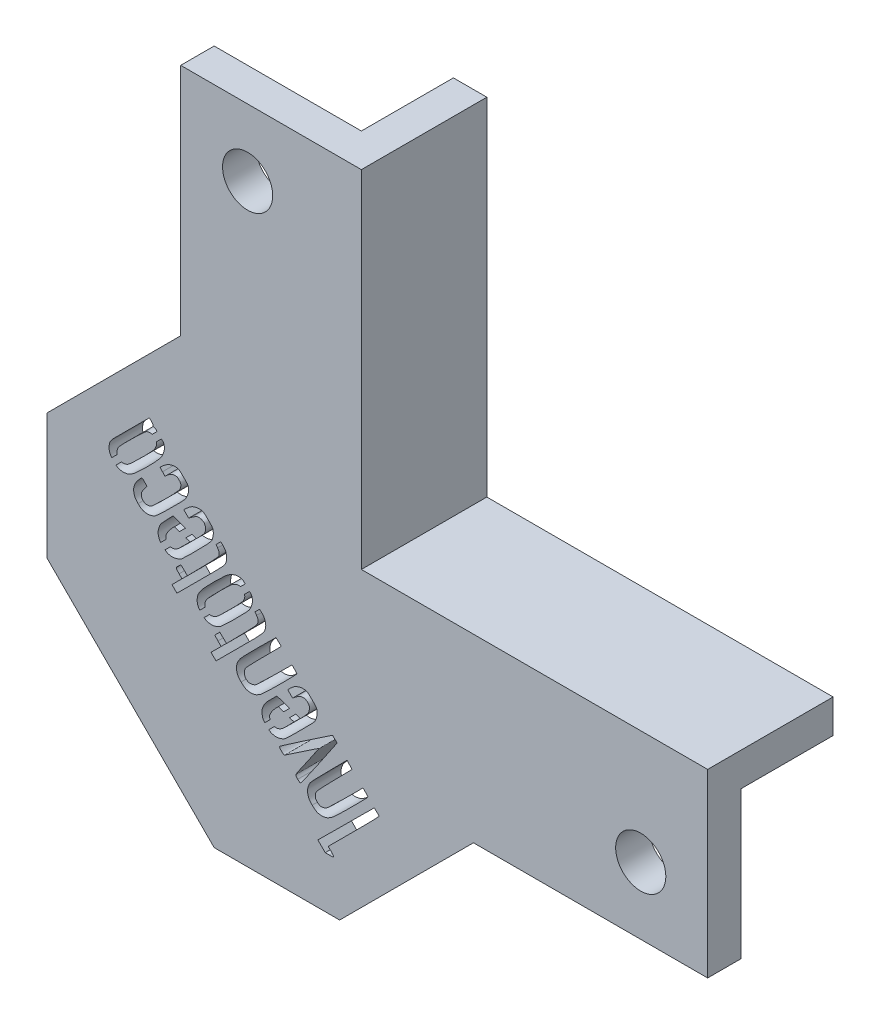
SolidWorks part; units mm, degrees
ref_plane "Alzado" through (0, 0, 0) normal (0, 0, 1) x (1, 0, 0)
ref_plane "Planta" through (0, 0, 0) normal (0, 1, 0) x (1, 0, 0)
ref_plane "Vista lateral" through (0, 0, 0) normal (1, 0, 0) x (0, 0, -1)
sketch "Croquis1" plane through (0, 0, 0) normal (0, 0, 1) x (1, 0, 0)
  line L0 (21.6725, 1.0791) -> (12.8725, 1.0791)
  line L5 (20.8725, 1.0791) -> (3.3725, 1.0791) construction
  line L6 (12.8725, 1.0791) -> (12.8725, -30.4209)
  line L7 (12.8725, -30.4209) -> (44.3725, -30.4209)
  line L8 (44.3725, -39.9209) -> (44.3725, -22.4209) construction
  line L9 (44.3725, -30.4209) -> (44.3725, -21.6209)
  line L10 (44.3725, -21.6209) -> (21.6725, -21.6209)
  line L12 (21.6725, -21.6209) -> (21.6725, 1.0791)
  line L13 (20.8725, -22.4209) -> (20.8725, 1.0791) construction
  line L14 (44.3725, -22.4209) -> (20.8725, -22.4209) construction
  circle A1 centre (16.8725, -2.9209) radius 1.5
  circle A2 centre (40.3725, -26.4209) radius 1.5
  dimension "D1" = 3
  dimension "D2" = 0.8
  dimension "D3" = 0.8
  dimension "D4" = 4
  dimension "D5" = 4
extrude "Saliente-Extruir1" add sketch "Croquis1" along normal blind 2
sketch "Croquis2" plane through (0, 0, 2) normal (0, 0, 1) x (1, 0, 0)
  line L0 (21.6725, 1.0791) -> (23.6725, 1.0791)
  line L1 (23.6725, 1.0791) -> (23.6725, -19.6209)
  line L2 (23.6725, -19.6209) -> (44.3725, -19.6209)
  line L3 (44.3725, -19.6209) -> (44.3725, -21.6209)
  line L4 (44.3725, -21.6209) -> (21.6725, -21.6209)
  line L5 (21.6725, -21.6209) -> (21.6725, 1.0791)
  dimension "D1" = 2
extrude "Saliente-Extruir2" add sketch "Croquis2" against normal blind 7.5
chamfer "Chaflán1" distance 4 angle 45 1 edges at (12.8725, -30.4209, 1)
sketch "Croquis3" plane through (0, 0, 2) normal (0, 0, 1) x (1, 0, 0)
  line L0 (32.3725, -19.6209) -> (23.6725, -19.6209)
  line L1 (23.6725, -10.9209) -> (4.8725, -10.9209)
  line L2 (32.3725, -19.6209) -> (32.3725, -38.4209)
  line L3 (32.3725, -38.4209) -> (4.8725, -38.4209)
  line L4 (4.8725, -10.9209) -> (4.8725, -38.4209)
  line L5 (23.6725, -19.6209) -> (23.6725, -10.9209)
  line L6 (23.6725, -19.6209) -> (23.6725, 1.0791) construction
  line L7 (44.3725, -19.6209) -> (23.6725, -19.6209) construction
  line L8 (12.8725, 1.0791) -> (12.8725, -26.4209) construction
  circle A0 centre (16.8725, -2.9209) radius 1.5 construction
  point P0 (35.2752, -19.6209)
  dimension "D1" = 8
  dimension "D2" = 8
extrude "Saliente-Extruir3" add sketch "Croquis3" against normal up to surface (2 mm away) up to face at (24.9582, -18.3352, 0)
chamfer "Chaflán2" distance 10 angle 45 5 edges at (4.8725, -38.4209, 1) (32.3725, -38.4209, 1) (4.8725, -10.9209, 1) (12.8725, -10.9209, 1) (32.3725, -30.4209, 1)
sketch "Croquis5" plane through (0, 0, 2) normal (0, 0, 1) x (1, 0, 0)
  line L101 (22.1338, -29.4646) -> (22.2205, -29.3331)
  line L102 (21.9537, -29.0664) -> (21.8212, -29.1522)
  line L103 (22.2205, -29.3331) -> (21.9537, -29.0664)
  line L104 (22.9663, -30.0879) -> (22.8171, -29.9252)
  line L105 (23.115, -30.2502) -> (22.9663, -30.0879)
  line L106 (22.0537, -31.3338) -> (23.115, -30.2502)
  line L107 (23.7698, -30.8824) -> (22.7028, -31.9495)
  line L108 (23.9208, -31.0332) -> (23.7698, -30.8824)
  line L109 (22.8171, -29.9252) -> (21.711, -31.0448)
  line L110 (20.2604, -28.9176) -> (20.0263, -29.1676)
  line L111 (19.5613, -28.3382) -> (19.731, -28.1996)
  line L112 (19.2698, -28.0468) -> (19.5613, -28.3382)
  line L113 (19.4261, -27.8905) -> (19.2698, -28.0468)
  line L114 (20.8043, -27.923) -> (20.7155, -27.8291)
  line L115 (20.8947, -28.0106) -> (20.8043, -27.923)
  line L116 (21.011, -28.2008) -> (21.0102, -28.2016)
  line L117 (21.0136, -28.2114) -> (21.011, -28.2008)
  line L118 (18.1359, -30.6851) -> (18.4694, -30.3516)
  line L119 (19.3823, -29.4387) -> (19.7472, -29.0738)
  line L120 (20.0263, -29.1676) -> (19.7472, -29.0738)
  line L121 (18.7262, -25.848) -> (18.5661, -25.7014)
  line L122 (18.8867, -25.995) -> (18.7262, -25.848)
  line L123 (17.8139, -27.081) -> (18.8867, -25.995)
  line L124 (19.525, -26.6376) -> (18.4515, -27.6982)
  line L125 (19.6694, -26.7821) -> (19.525, -26.6376)
  line L126 (18.5661, -25.7014) -> (17.5655, -26.6898)
  line L127 (15.1002, -27.6067) -> (15.2844, -27.8035)
  line L128 (15.2055, -27.1034) -> (14.9078, -27.4012)
  line L129 (15.4128, -27.2975) -> (15.2055, -27.1034)
  line L130 (17.5868, -24.7221) -> (17.313, -24.996)
  line L131 (17.7195, -24.8425) -> (17.5868, -24.7221)
  line L132 (14.9831, -28.7009) -> (16.3714, -27.3125)
  line L133 (14.6851, -28.4028) -> (14.9831, -28.7009)
  line L134 (15.2844, -27.8035) -> (14.6851, -28.4028)
  line L135 (14.9078, -27.4012) -> (15.1002, -27.6067)
  line L136 (15.6113, -27.4834) -> (15.4128, -27.2975)
  line L137 (16.5166, -26.5629) -> (15.6113, -27.4834)
  line L138 (17.313, -24.996) -> (17.4085, -25.1299)
  line L139 (16.728, -23.8437) -> (16.7279, -23.8435)
  line L140 (16.4374, -24.1343) -> (16.728, -23.8437)
  line L141 (14.0131, -26.5586) -> (14.3374, -26.2343)
  line L142 (12.3482, -26.066) -> (12.6462, -26.364)
  line L143 (12.9491, -25.4651) -> (12.3482, -26.066)
  line L144 (14.1896, -24.2154) -> (13.272, -25.1474)
  line L145 (14.9807, -22.6768) -> (15.0771, -22.8027)
  line L146 (15.2725, -22.385) -> (14.9807, -22.6768)
  line L147 (15.3914, -22.5086) -> (15.2725, -22.385)
  line L148 (12.6462, -26.364) -> (14.0486, -24.9616)
  line L149 (12.7784, -25.2941) -> (12.9491, -25.4651)
  line L150 (13.272, -25.1474) -> (13.0859, -24.9613)
  line L151 (12.4918, -23.002) -> (12.7939, -23.1024)
  line L152 (12.3893, -23.1052) -> (12.4918, -23.002)
  line L153 (11.6745, -24.2218) -> (12.0003, -23.896)
  line L154 (12.4077, -22.4815) -> (12.0343, -22.8714)
  line L155 (13.1109, -22.7223) -> (12.4077, -22.4815)
  line L156 (13.1579, -22.7384) -> (13.1109, -22.7223)
  line L157 (12.7939, -23.1024) -> (13.1579, -22.7384)
  line L158 (11.9318, -20.6687) -> (12.0141, -20.5864)
  line L159 (11.7838, -20.5072) -> (11.9318, -20.6687)
  line L160 (11.636, -20.3458) -> (11.7838, -20.5072)
  line L161 (11.8156, -20.1828) -> (11.636, -20.3458)
  line L162 (13.1533, -20.2692) -> (12.8873, -20.0029)
  line L163 (10.7039, -21.9191) -> (10.8499, -21.7242)
  line L164 (10.8499, -21.7242) -> (10.7175, -21.5783)
  line L165 (9.007, -21.5496) -> (9.335, -21.2216)
  line L166 (11.4289, -19.1277) -> (11.7197, -18.8368)
  line L167 (11.7602, -18.8774) -> (11.7197, -18.8368)
  line L168 (24.5869, -31.7089) -> (24.4416, -31.577)
  line L169 (21.6908, -34.9461) -> (23.2073, -33.4296)
  line L170 (21.8644, -35.1198) -> (21.6908, -34.9461)
  line L171 (21.5113, -35.3625) -> (21.7474, -35.364)
  line L172 (21.0722, -34.9235) -> (21.5112, -35.3625)
  line L173 (22.7571, -33.2501) -> (21.0722, -34.9235)
  line L174 (24.4416, -31.577) -> (22.7571, -33.2501)
  line L175 (16.8244, -23.94) -> (16.728, -23.8437)
  line L176 (17.1301, -24.2886) -> (17.1292, -24.2896)
  line L177 (17.133, -24.2986) -> (17.1301, -24.2886)
  line L178 (14.2709, -26.8134) -> (14.598, -26.4862)
  line L179 (16.6861, -24.3981) -> (16.9832, -24.1011)
  line L180 (17.0216, -24.1387) -> (16.9832, -24.1011)
  line L181 (14.0184, -22.7485) -> (13.8067, -22.9606)
  line L182 (13.349, -22.1259) -> (13.5387, -21.984)
  line L183 (13.0548, -21.8317) -> (13.349, -22.1259)
  line L184 (13.264, -21.6424) -> (13.0548, -21.8317)
  line L185 (14.441, -21.5561) -> (14.357, -21.4709)
  line L186 (14.6862, -21.8005) -> (14.5965, -21.712)
  line L187 (11.9331, -24.4757) -> (12.2602, -24.1478)
  line L188 (13.1778, -23.2311) -> (13.5397, -22.8691)
  line L189 (13.8067, -22.9606) -> (13.5397, -22.8691)
  line L190 (8.7473, -21.2967) -> (9.071, -20.973)
  line L191 (8.8451, -20.2606) -> (8.7972, -20.3096)
  line L192 (10.9676, -18.1383) -> (8.8451, -20.2606)
  line L193 (11.4646, -18.5795) -> (11.4523, -18.5669)
  line L194 (11.1713, -18.8727) -> (11.4646, -18.5795)
  line L195 (18.7012, -29.2114) -> (19.0213, -29.3178)
  line L196 (18.6211, -28.6954) -> (18.281, -29.0356)
  line L197 (19.0213, -29.3178) -> (19.3864, -28.9526)
  line L198 (18.5654, -29.3481) -> (18.7012, -29.2114)
  line L199 (19.3864, -28.9526) -> (19.3274, -28.9328)
  line L200 (17.8967, -30.4424) -> (18.2171, -30.122)
  line L201 (19.3274, -28.9328) -> (18.6211, -28.6954)
  spline S48 degree 3 number of poles 84 (19.8674, -32.3833) -> (22.1338, -29.4646)
  spline S49 degree 3 number of poles 313 (21.8212, -29.1522) -> (19.8674, -32.3833)
  spline S50 degree 3 number of poles 66 (22.7028, -31.9495) -> (22.0537, -31.3338)
  spline S51 degree 3 number of poles 147 (20.7312, -33.2907) -> (23.9208, -31.0332)
  spline S52 degree 3 poles (21.711, -31.0448) (21.6605, -31.0959) (21.5594, -31.1982) (21.4079, -31.3518) (21.2723, -31.4894) (21.1526, -31.6112) (21.0489, -31.7171) (20.9578, -31.8109) (20.8793, -31.8925) (20.8134, -31.9619) (20.7568, -32.0227) (20.7093, -32.075) (20.6711, -32.1187) (20.6391, -32.1579) (20.613, -32.1922) (20.5927, -32.2214) (20.5755, -32.2496) (20.5613, -32.2768) (20.5494, -32.3023) (20.5373, -32.3308) (20.5249, -32.362) (20.5123, -32.3961) (20.5005, -32.4308) (20.4894, -32.466) (20.479, -32.5018) (20.4697, -32.5356) (20.4616, -32.5674) (20.455, -32.5972) (20.4503, -32.6273) (20.4481, -32.6577) (20.448, -32.6882) (20.4496, -32.7208) (20.4528, -32.7556) (20.4577, -32.7924) (20.4642, -32.8288) (20.472, -32.8647) (20.4811, -32.9002) (20.4922, -32.9379) (20.5057, -32.9777) (20.5222, -33.0191) (20.5413, -33.0586) (20.5631, -33.096) (20.5871, -33.1312) (20.6162, -33.1688) (20.6507, -33.2085) (20.6905, -33.25) (20.7176, -33.2771) (20.7312, -33.2907) knots 0 0 0 0 0.076954 0.153907 0.23086 0.283751 0.336642 0.389535 0.423665 0.457793 0.491917 0.512625 0.533334 0.554061 0.56676 0.579445 0.592109 0.602148 0.612198 0.622257 0.63523 0.648193 0.661148 0.67443 0.687719 0.701028 0.711935 0.722825 0.733689 0.744526 0.755392 0.766273 0.779524 0.79276 0.805987 0.819044 0.832109 0.845188 0.861108 0.877014 0.892899 0.908066 0.923252 0.938439 0.958952 0.979467 1 1 1 1
  spline S53 degree 3 poles (19.731, -28.1996) (19.7421, -28.1912) (19.7644, -28.1743) (19.7982, -28.1493) (19.8326, -28.1251) (19.868, -28.1022) (19.9041, -28.0804) (19.9384, -28.0611) (19.9706, -28.044) (20.0007, -28.0296) (20.0301, -28.0177) (20.0586, -28.0087) (20.086, -28.0018) (20.1136, -27.9962) (20.1414, -27.9918) (20.1693, -27.9884) (20.1955, -27.9865) (20.2197, -27.9857) (20.242, -27.9865) (20.2638, -27.9895) (20.2849, -27.9953) (20.3051, -28.0031) (20.3263, -28.013) (20.3485, -28.0245) (20.3715, -28.0378) (20.3937, -28.0521) (20.415, -28.0672) (20.4354, -28.0833) (20.4553, -28.1009) (20.4744, -28.12) (20.4926, -28.1407) (20.5088, -28.1621) (20.5232, -28.1838) (20.5356, -28.2058) (20.5462, -28.2282) (20.5549, -28.2511) (20.5615, -28.2742) (20.5661, -28.2978) (20.5685, -28.3216) (20.569, -28.3455) (20.5682, -28.371) (20.5663, -28.3981) (20.5631, -28.4266) (20.5589, -28.4547) (20.5537, -28.4822) (20.5474, -28.509) (20.5388, -28.5385) (20.5268, -28.5702) (20.511, -28.6036) (20.4911, -28.6395) (20.4664, -28.6772) (20.4371, -28.7166) (20.4012, -28.7608) (20.3588, -28.81) (20.3099, -28.8641) (20.2769, -28.8998) (20.2604, -28.9176) knots 0 0 0 0 0.023887 0.04776 0.071615 0.095597 0.119599 0.143636 0.16267 0.181678 0.20065 0.216663 0.232697 0.248731 0.264704 0.280675 0.296702 0.3094 0.322053 0.334625 0.346885 0.359222 0.371603 0.386744 0.401832 0.416908 0.431672 0.446445 0.461221 0.476881 0.492541 0.508205 0.522549 0.53689 0.551238 0.564907 0.578568 0.5922 0.605757 0.619335 0.63293 0.649283 0.665616 0.681953 0.697636 0.713316 0.728986 0.749973 0.77099 0.792012 0.819891 0.847772 0.875671 0.917131 0.958567 1 1 1 1
  spline S54 degree 3 number of poles 66 (20.6224, -27.7411) -> (19.4261, -27.8905)
  spline S55 degree 3 poles (20.7155, -27.8291) (20.7086, -27.8243) (20.6937, -27.814) (20.671, -27.7931) (20.6545, -27.7698) (20.6415, -27.7511) (20.6348, -27.7381) (20.6247, -27.7381) (20.6228, -27.7406) (20.6226, -27.7408) (20.6224, -27.741) (20.6224, -27.7411) knots 0 0 0 0 0.188249 0.405775 0.68873 0.822663 0.92833 0.992253 0.994929 0.998086 1 1 1 1
  spline S56 degree 3 poles (21.0102, -28.2016) (21.0075, -28.1941) (21.0019, -28.1791) (20.9932, -28.1567) (20.9832, -28.134) (20.9715, -28.1114) (20.958, -28.0889) (20.9432, -28.0677) (20.9275, -28.0479) (20.9113, -28.0291) (20.9002, -28.0168) (20.8947, -28.0106) knots 0 0 0 0 0.106664 0.213276 0.319826 0.436244 0.552766 0.669193 0.779404 0.889656 1 1 1 1
  spline S57 degree 3 number of poles 81 (18.1359, -30.6851) -> (21.0136, -28.2114)
  spline S58 degree 3 number of poles 96 (19.3823, -29.4387) -> (18.4694, -30.3516)
  spline S59 degree 3 number of poles 84 (18.4515, -27.6982) -> (17.8139, -27.081)
  spline S60 degree 3 number of poles 102 (18.8171, -27.9823) -> (19.6694, -26.7821)
  spline S61 degree 3 number of poles 66 (16.482, -29.0405) -> (18.8171, -27.9823)
  spline S62 degree 3 poles (17.5655, -26.6898) (17.5327, -26.7222) (17.4672, -26.7871) (17.369, -26.8845) (17.275, -26.9781) (17.1852, -27.0679) (17.0995, -27.154) (17.0185, -27.2358) (16.942, -27.3134) (16.8701, -27.3867) (16.8032, -27.4554) (16.7414, -27.5194) (16.6846, -27.5787) (16.6332, -27.6328) (16.5871, -27.6819) (16.5465, -27.7258) (16.5118, -27.7643) (16.4828, -27.7973) (16.4596, -27.8248) (16.4357, -27.8548) (16.4117, -27.888) (16.3875, -27.9242) (16.3644, -27.9608) (16.3418, -27.9976) (16.32, -28.0346) (16.3004, -28.0694) (16.283, -28.1018) (16.2682, -28.1321) (16.2554, -28.162) (16.2451, -28.1918) (16.2367, -28.221) (16.2291, -28.2518) (16.2223, -28.2842) (16.2162, -28.3181) (16.2113, -28.3512) (16.2076, -28.3836) (16.2051, -28.4152) (16.2042, -28.4468) (16.205, -28.4785) (16.2074, -28.51) (16.2111, -28.5424) (16.2158, -28.5755) (16.2217, -28.6093) (16.2283, -28.6417) (16.2356, -28.6724) (16.2437, -28.7015) (16.2539, -28.7317) (16.2668, -28.7625) (16.2826, -28.7937) (16.3014, -28.826) (16.3233, -28.859) (16.3482, -28.8926) (16.3769, -28.9279) (16.4094, -28.9645) (16.4454, -29.0028) (16.4698, -29.0279) (16.482, -29.0405) knots 0 0 0 0 0.046922 0.093844 0.140766 0.181957 0.223148 0.264339 0.299181 0.334023 0.368865 0.396731 0.424597 0.452461 0.472756 0.493052 0.513356 0.525548 0.537735 0.549913 0.564652 0.579401 0.594152 0.60874 0.623324 0.637921 0.649361 0.66079 0.672201 0.682489 0.692793 0.703103 0.714791 0.726471 0.738155 0.748906 0.759652 0.770389 0.781115 0.791849 0.802586 0.81424 0.825891 0.837548 0.847809 0.858062 0.868305 0.880162 0.892037 0.903919 0.918126 0.932328 0.946527 0.964346 0.982167 1 1 1 1
  spline S63 degree 3 poles (16.3714, -27.3125) (16.4716, -27.2122) (16.6719, -27.0117) (16.9718, -26.7106) (17.2193, -26.4608) (17.4147, -26.2625) (17.5574, -26.1143) (17.6695, -25.993) (17.7519, -25.8999) (17.8038, -25.8348) (17.8412, -25.7778) (17.8659, -25.7309) (17.8819, -25.6963) (17.8967, -25.6605) (17.9106, -25.6237) (17.9234, -25.5858) (17.9343, -25.5494) (17.9435, -25.5146) (17.9505, -25.4814) (17.9551, -25.4479) (17.9569, -25.4143) (17.9563, -25.3809) (17.954, -25.3457) (17.9502, -25.3089) (17.9448, -25.2707) (17.938, -25.2334) (17.9298, -25.1972) (17.9204, -25.1621) (17.909, -25.1263) (17.8956, -25.0899) (17.8797, -25.0533) (17.8624, -25.0187) (17.8436, -24.9863) (17.8237, -24.9561) (17.8012, -24.9265) (17.7757, -24.8979) (17.748, -24.8699) (17.729, -24.8517) (17.7195, -24.8425) knots 0 0 0 0 0.135053 0.270019 0.404809 0.469989 0.535254 0.600769 0.627289 0.653702 0.679993 0.692074 0.704181 0.716295 0.728979 0.741656 0.754349 0.765151 0.77594 0.786701 0.797302 0.807927 0.818568 0.830853 0.843119 0.855381 0.866918 0.878459 0.890001 0.902685 0.915369 0.928061 0.939535 0.951001 0.962446 0.97494 0.987458 1 1 1 1
  spline S64 degree 3 poles (17.4085, -25.1299) (17.4112, -25.134) (17.4167, -25.1422) (17.425, -25.1544) (17.433, -25.1669) (17.4407, -25.1796) (17.4481, -25.1925) (17.4552, -25.2054) (17.462, -25.2182) (17.4685, -25.231) (17.4744, -25.2436) (17.48, -25.2559) (17.4851, -25.268) (17.4896, -25.2795) (17.4937, -25.2905) (17.4971, -25.301) (17.4999, -25.3108) (17.502, -25.3198) (17.5035, -25.3279) (17.505, -25.3394) (17.5053, -25.3543) (17.5037, -25.3725) (17.5008, -25.3922) (17.4972, -25.4136) (17.4927, -25.4365) (17.4877, -25.4594) (17.4821, -25.4822) (17.4754, -25.5048) (17.464, -25.5365) (17.4435, -25.5755) (17.4121, -25.6199) (17.3598, -25.6836) (17.2875, -25.7663) (17.1942, -25.8667) (17.0669, -25.9991) (16.9062, -26.1648) (16.7117, -26.3639) (16.5817, -26.4965) (16.5166, -26.5629) knots 0 0 0 0 0.008054 0.016101 0.024145 0.032273 0.040403 0.048533 0.056353 0.064173 0.071995 0.079125 0.086254 0.093384 0.099417 0.105447 0.111481 0.116016 0.120547 0.125064 0.134938 0.144863 0.154825 0.167602 0.180333 0.193075 0.205934 0.218779 0.231568 0.260919 0.290556 0.320438 0.395636 0.470247 0.544663 0.696109 0.847954 1 1 1 1
  spline S65 degree 3 number of poles 90 (16.7279, -23.8435) -> (14.0131, -26.5586)
  spline S66 degree 3 number of poles 75 (14.3374, -26.2343) -> (16.4374, -24.1343)
  spline S67 degree 3 poles (15.0771, -22.8027) (15.0827, -22.8108) (15.0938, -22.827) (15.11, -22.8518) (15.1249, -22.8766) (15.1379, -22.9018) (15.1492, -22.9272) (15.1582, -22.9514) (15.1651, -22.9741) (15.1699, -22.9954) (15.1727, -23.0163) (15.173, -23.0367) (15.1718, -23.0565) (15.1695, -23.0768) (15.1665, -23.0978) (15.1629, -23.1193) (15.1591, -23.1399) (15.1553, -23.1596) (15.1504, -23.1782) (15.1451, -23.1924) (15.1398, -23.2022) (15.1363, -23.2084) (15.1315, -23.216) (15.1252, -23.2249) (15.1177, -23.2351) (15.1088, -23.2465) (15.0985, -23.2592) (15.0871, -23.2732) (15.0743, -23.2885) (15.0602, -23.305) (15.0447, -23.3227) (15.0278, -23.3418) (15.0096, -23.3622) (14.99, -23.3838) (14.969, -23.4069) (14.9465, -23.4311) (14.9228, -23.4569) (14.8869, -23.4955) (14.8386, -23.5467) (14.778, -23.6105) (14.7114, -23.6801) (14.6388, -23.7555) (14.5603, -23.8366) (14.4754, -23.9238) (14.3843, -24.017) (14.287, -24.1162) (14.222, -24.1823) (14.1896, -24.2154) knots 0 0 0 0 0.016293 0.032566 0.048818 0.064073 0.07935 0.094665 0.106673 0.118646 0.130568 0.141434 0.152339 0.163257 0.175252 0.187232 0.199261 0.209865 0.220424 0.230917 0.234846 0.238794 0.242748 0.249721 0.256692 0.263664 0.273622 0.283583 0.293544 0.306514 0.319483 0.332454 0.348541 0.364629 0.380716 0.399995 0.419277 0.438558 0.487012 0.535467 0.583922 0.646094 0.708267 0.770442 0.846961 0.923481 1 1 1 1
  spline S68 degree 3 poles (14.0486, -24.9616) (14.1498, -24.8602) (14.352, -24.6575) (14.6549, -24.3532) (14.9049, -24.1014) (15.1021, -23.9018) (15.2457, -23.7532) (15.3576, -23.6316) (15.4391, -23.5387) (15.4898, -23.4747) (15.5272, -23.4177) (15.5527, -23.3695) (15.5694, -23.332) (15.5835, -23.2938) (15.5949, -23.2552) (15.6036, -23.2164) (15.6103, -23.1753) (15.6146, -23.1319) (15.6166, -23.0864) (15.6163, -23.0428) (15.6147, -23.0014) (15.6118, -22.962) (15.6076, -22.9235) (15.6023, -22.8856) (15.5957, -22.8486) (15.5882, -22.8148) (15.5801, -22.7842) (15.5712, -22.757) (15.5603, -22.7312) (15.5471, -22.7072) (15.5325, -22.6846) (15.5158, -22.6608) (15.4975, -22.6354) (15.4775, -22.6088) (15.4569, -22.5828) (15.4355, -22.5577) (15.4136, -22.533) (15.3988, -22.5168) (15.3914, -22.5086) knots 0 0 0 0 0.137335 0.2746 0.411726 0.477673 0.543686 0.609908 0.636091 0.662186 0.688191 0.701312 0.714451 0.727591 0.740295 0.752996 0.765692 0.780246 0.794804 0.809369 0.821984 0.834589 0.847187 0.859194 0.871208 0.883249 0.892412 0.901551 0.910652 0.919222 0.927824 0.936446 0.947117 0.957762 0.968396 0.978921 0.989457 1 1 1 1
  spline S69 degree 3 number of poles 84 (13.0859, -24.9613) -> (12.7784, -25.2941)
  spline S70 degree 3 poles (12.0003, -23.896) (12.0003, -23.896) (12.0002, -23.8958) (12.0001, -23.8957) (11.9968, -23.8902) (11.9933, -23.8781) (11.9868, -23.8608) (11.9824, -23.8426) (11.9801, -23.8241) (11.9795, -23.8052) (11.9802, -23.7845) (11.982, -23.7621) (11.985, -23.7381) (11.9892, -23.7141) (11.9942, -23.6902) (12.0004, -23.6664) (12.0084, -23.6414) (12.0189, -23.6154) (12.0316, -23.5884) (12.0467, -23.5595) (12.0636, -23.5284) (12.0827, -23.4953) (12.1027, -23.4627) (12.1234, -23.4304) (12.1449, -23.3987) (12.1675, -23.3671) (12.1912, -23.3359) (12.2158, -23.3049) (12.2411, -23.2737) (12.2669, -23.2423) (12.2934, -23.2108) (12.3188, -23.1816) (12.3432, -23.1547) (12.3662, -23.1299) (12.3816, -23.1134) (12.3893, -23.1052) knots 0 0 0 0 0.000183 0.000383 0.000648 0.020829 0.040952 0.060974 0.081322 0.101778 0.12229 0.148627 0.174894 0.201162 0.227787 0.254417 0.281015 0.313263 0.345572 0.377916 0.419388 0.460817 0.502237 0.543859 0.58549 0.627117 0.670055 0.712996 0.755948 0.800627 0.845299 0.889961 0.926634 0.963315 1 1 1 1
  spline S71 degree 3 poles (12.0343, -22.8714) (12.0175, -22.889) (11.9839, -22.9241) (11.9335, -22.9769) (11.888, -23.0249) (11.8476, -23.0682) (11.8121, -23.1066) (11.7804, -23.142) (11.7523, -23.1741) (11.7281, -23.2031) (11.7066, -23.2306) (11.6876, -23.2565) (11.6713, -23.2808) (11.6564, -23.3051) (11.6432, -23.3295) (11.6313, -23.3537) (11.6196, -23.3795) (11.6082, -23.4067) (11.597, -23.4354) (11.5851, -23.4679) (11.5727, -23.5044) (11.5603, -23.545) (11.5492, -23.5857) (11.5396, -23.6265) (11.5315, -23.6673) (11.5254, -23.7055) (11.521, -23.741) (11.5187, -23.7736) (11.5188, -23.8053) (11.5216, -23.8359) (11.5263, -23.8654) (11.5326, -23.8961) (11.5399, -23.928) (11.5484, -23.9612) (11.5577, -23.9933) (11.5677, -24.0243) (11.5786, -24.0542) (11.5903, -24.0825) (11.6028, -24.109) (11.6159, -24.1338) (11.6297, -24.1575) (11.644, -24.1799) (11.6588, -24.2012) (11.6693, -24.2149) (11.6745, -24.2218) knots 0 0 0 0 0.047071 0.094142 0.141214 0.174995 0.208773 0.242553 0.266903 0.291256 0.315615 0.334502 0.353384 0.372253 0.389659 0.407073 0.424492 0.444351 0.464206 0.484067 0.511452 0.538836 0.566208 0.593045 0.619896 0.646794 0.66792 0.689005 0.710026 0.729214 0.748451 0.767717 0.789822 0.81189 0.833956 0.854477 0.875006 0.895529 0.913632 0.931739 0.949851 0.966571 0.983287 1 1 1 1
  spline S72 degree 3 number of poles 75 (11.9809, -21.8038) -> (10.7039, -21.9191)
  spline S73 degree 3 number of poles 84 (12.0141, -20.5864) -> (11.9809, -21.8038)
  spline S74 degree 3 poles (12.8873, -20.0029) (12.8813, -19.9974) (12.8692, -19.9864) (12.8509, -19.9701) (12.8316, -19.9543) (12.8112, -19.9394) (12.7897, -19.9254) (12.7685, -19.913) (12.7479, -19.902) (12.7278, -19.8927) (12.7068, -19.8847) (12.6846, -19.8786) (12.6616, -19.8742) (12.6366, -19.8706) (12.6096, -19.8675) (12.5807, -19.8651) (12.5518, -19.8634) (12.5229, -19.8625) (12.494, -19.8625) (12.464, -19.864) (12.4328, -19.8674) (12.4007, -19.8726) (12.3669, -19.8795) (12.3314, -19.8879) (12.2944, -19.8981) (12.2582, -19.9091) (12.2229, -19.921) (12.1886, -19.9338) (12.1536, -19.9488) (12.1184, -19.9665) (12.0828, -19.9866) (12.0456, -20.0095) (12.0066, -20.0347) (11.9661, -20.0626) (11.9268, -20.0915) (11.8889, -20.1214) (11.8521, -20.1519) (11.8277, -20.1725) (11.8156, -20.1828) knots 0 0 0 0 0.020498 0.04096 0.061397 0.08282 0.104279 0.125785 0.144309 0.162786 0.181204 0.200699 0.220263 0.239868 0.264107 0.288305 0.312503 0.33663 0.360758 0.384869 0.412028 0.439216 0.466416 0.498508 0.530586 0.562679 0.593284 0.623871 0.654422 0.688517 0.722657 0.756827 0.797971 0.839077 0.88016 0.920086 0.960033 1 1 1 1
  spline S75 degree 3 number of poles 102 (10.3244, -22.8849) -> (13.1533, -20.2692)
  spline S76 degree 3 number of poles 93 (10.7175, -21.5783) -> (10.3244, -22.8849)
  spline S77 degree 3 poles (11.4289, -19.1277) (11.4293, -19.1293) (11.4302, -19.1325) (11.4314, -19.1374) (11.4341, -19.1492) (11.4373, -19.1681) (11.4396, -19.1942) (11.4403, -19.2211) (11.4393, -19.2485) (11.4364, -19.2765) (11.4312, -19.3055) (11.4232, -19.3352) (11.4126, -19.3657) (11.3994, -19.3982) (11.384, -19.433) (11.3661, -19.4697) (11.3469, -19.506) (11.3266, -19.5418) (11.305, -19.577) (11.2757, -19.6206) (11.2365, -19.6711) (11.1869, -19.7278) (11.1224, -19.797) (11.0444, -19.8798) (10.9525, -19.9758) (10.8477, -20.0835) (10.7295, -20.2025) (10.598, -20.3329) (10.4789, -20.4501) (10.3725, -20.5541) (10.279, -20.6454) (10.1947, -20.7276) (10.1195, -20.8004) (10.0534, -20.8641) (9.9942, -20.9203) (9.942, -20.9693) (9.8966, -21.0108) (9.8561, -21.047) (9.8203, -21.0776) (9.7895, -21.1029) (9.761, -21.1244) (9.735, -21.1423) (9.7117, -21.1567) (9.6888, -21.1693) (9.6661, -21.1801) (9.6439, -21.1893) (9.6191, -21.1985) (9.5918, -21.2074) (9.5618, -21.2157) (9.5317, -21.2225) (9.5015, -21.2281) (9.4712, -21.2322) (9.4429, -21.2346) (9.4169, -21.2357) (9.3931, -21.2351) (9.3734, -21.2327) (9.3579, -21.2291) (9.3464, -21.2257) (9.3388, -21.223) (9.335, -21.2216) knots 0 0 0 0 0.00162 0.003237 0.004853 0.013248 0.021643 0.030049 0.039059 0.048064 0.057052 0.067355 0.077676 0.088011 0.101133 0.114239 0.127347 0.140583 0.153815 0.167035 0.19113 0.215271 0.23945 0.282114 0.324714 0.367294 0.426655 0.486045 0.545442 0.587334 0.629221 0.671108 0.700529 0.729951 0.759371 0.779087 0.798804 0.818526 0.831321 0.844111 0.856902 0.865666 0.874427 0.88318 0.890878 0.898581 0.906288 0.916261 0.926232 0.936195 0.945977 0.955768 0.965593 0.973233 0.980845 0.988411 0.992265 0.996128 1 1 1 1
  spline S78 degree 3 number of poles 81 (9.007, -21.5496) -> (11.7602, -18.8774)
  spline S79 degree 3 number of poles 102 (23.2073, -33.4296) -> (24.5869, -31.7089)
  spline S80 degree 3 poles (21.7474, -35.364) (21.7544, -35.364) (21.7684, -35.3639) (21.7895, -35.3638) (21.8101, -35.3634) (21.8302, -35.3628) (21.8498, -35.362) (21.8687, -35.3609) (21.8868, -35.3597) (21.9041, -35.3583) (21.9182, -35.357) (21.929, -35.3558) (21.9366, -35.3549) (21.9439, -35.354) (21.9509, -35.3531) (21.9576, -35.3521) (21.9639, -35.3511) (21.97, -35.35) (21.9757, -35.3489) (21.9811, -35.3478) (21.9861, -35.3467) (21.9908, -35.3456) (21.9951, -35.3444) (21.9991, -35.3433) (22.0027, -35.342) (22.006, -35.3406) (22.009, -35.339) (22.0116, -35.3372) (22.014, -35.3351) (22.0161, -35.3327) (22.0179, -35.33) (22.0192, -35.3271) (22.0202, -35.3239) (22.0208, -35.3206) (22.021, -35.3172) (22.0207, -35.3136) (22.0202, -35.3099) (22.0193, -35.3061) (22.0181, -35.3021) (22.0165, -35.2981) (22.0146, -35.2939) (22.0123, -35.2895) (22.0098, -35.2849) (22.0069, -35.2801) (22.0037, -35.2751) (22.0001, -35.2699) (21.9946, -35.2621) (21.9868, -35.2518) (21.9766, -35.2392) (21.9649, -35.2254) (21.9518, -35.2105) (21.9372, -35.1946) (21.921, -35.1774) (21.9032, -35.1591) (21.8839, -35.1393) (21.8709, -35.1263) (21.8644, -35.1198) knots 0 0 0 0 0.038633 0.077264 0.115893 0.151934 0.187968 0.224006 0.25596 0.287915 0.319858 0.333847 0.347823 0.361798 0.374215 0.386639 0.399073 0.409773 0.420491 0.431197 0.439995 0.448802 0.457599 0.464611 0.471632 0.478674 0.484488 0.490289 0.496078 0.501927 0.507779 0.513624 0.519745 0.525876 0.532003 0.538771 0.545627 0.55249 0.56049 0.56843 0.576372 0.58596 0.595565 0.605164 0.616699 0.628242 0.639797 0.669572 0.69936 0.729153 0.768858 0.808544 0.848224 0.89881 0.949404 1 1 1 1
  spline S81 degree 3 poles (16.8244, -23.94) (16.8213, -23.9369) (16.8152, -23.9305) (16.806, -23.921) (16.7923, -23.9071) (16.774, -23.8887) (16.7511, -23.8662) (16.7357, -23.8512) (16.728, -23.8437) knots 0 0 0 0 0.097055 0.194104 0.29115 0.527411 0.7637 1 1 1 1
  spline S82 degree 3 poles (17.1292, -24.2896) (17.1282, -24.2873) (17.1262, -24.2827) (17.1233, -24.2759) (17.12, -24.2688) (17.1162, -24.2614) (17.112, -24.2539) (17.1075, -24.2461) (17.1025, -24.2382) (17.0972, -24.2301) (17.0913, -24.2214) (17.0848, -24.2122) (17.0776, -24.2026) (17.0701, -24.193) (17.0625, -24.1835) (17.0546, -24.174) (17.0466, -24.1648) (17.0383, -24.156) (17.03, -24.1472) (17.0244, -24.1415) (17.0216, -24.1387) knots 0 0 0 0 0.039885 0.079871 0.119853 0.166107 0.212403 0.258728 0.310794 0.362868 0.414943 0.479531 0.544057 0.608592 0.674591 0.740603 0.806606 0.871056 0.935522 1 1 1 1
  spline S83 degree 3 number of poles 93 (14.2709, -26.8134) -> (17.133, -24.2986)
  spline S84 degree 3 poles (16.6861, -24.3981) (16.6874, -24.4038) (16.6899, -24.4151) (16.6932, -24.4322) (16.6963, -24.4501) (16.6993, -24.469) (16.7016, -24.4888) (16.7025, -24.5096) (16.7012, -24.5313) (16.6979, -24.5537) (16.6927, -24.5783) (16.6857, -24.6051) (16.6767, -24.6338) (16.6664, -24.6625) (16.655, -24.6913) (16.6423, -24.7198) (16.6237, -24.7564) (16.5966, -24.7996) (16.5599, -24.8481) (16.508, -24.9101) (16.4413, -24.9854) (16.3591, -25.0734) (16.254, -25.1824) (16.1263, -25.313) (15.9758, -25.4651) (15.8246, -25.6165) (15.6733, -25.7677) (15.5214, -25.9181) (15.3909, -26.0456) (15.2818, -26.1505) (15.1937, -26.2327) (15.1184, -26.2996) (15.0566, -26.3518) (15.0081, -26.3885) (14.9645, -26.4158) (14.9267, -26.4346) (14.8964, -26.4476) (14.8652, -26.4591) (14.8333, -26.4695) (14.8008, -26.4783) (14.7693, -26.4851) (14.7391, -26.4898) (14.7101, -26.4927) (14.6814, -26.494) (14.6531, -26.4938) (14.6253, -26.4917) (14.6071, -26.4881) (14.598, -26.4862) knots 0 0 0 0 0.005598 0.011195 0.016802 0.023224 0.029639 0.036033 0.043303 0.050601 0.057914 0.067622 0.077313 0.087008 0.09708 0.107148 0.117198 0.136713 0.156302 0.17595 0.2148 0.253538 0.292245 0.361104 0.430022 0.498974 0.56785 0.636693 0.705464 0.744188 0.782952 0.821844 0.841492 0.861072 0.880563 0.891161 0.901785 0.912425 0.923295 0.934148 0.944986 0.954347 0.96372 0.973117 0.982098 0.991063 1 1 1 1
  spline S85 degree 3 number of poles 66 (13.5387, -21.984) -> (14.0184, -22.7485)
  spline S86 degree 3 poles (14.357, -21.4709) (14.351, -21.4655) (14.3389, -21.4546) (14.3206, -21.4385) (14.3014, -21.4231) (14.2811, -21.4084) (14.2599, -21.3947) (14.239, -21.3826) (14.2188, -21.3719) (14.1992, -21.3629) (14.1786, -21.3551) (14.157, -21.3492) (14.1345, -21.3447) (14.1099, -21.3409) (14.0834, -21.3374) (14.0548, -21.3344) (14.0262, -21.332) (13.9975, -21.3301) (13.9687, -21.3292) (13.9388, -21.3295) (13.9077, -21.3314) (13.8756, -21.3349) (13.8419, -21.3398) (13.8066, -21.3462) (13.7697, -21.354) (13.7338, -21.3627) (13.6988, -21.3722) (13.6649, -21.3826) (13.6293, -21.3952) (13.5924, -21.4106) (13.5544, -21.4289) (13.5156, -21.4501) (13.4763, -21.4742) (13.4364, -21.5012) (13.395, -21.5318) (13.3522, -21.5662) (13.3079, -21.604) (13.2786, -21.6296) (13.264, -21.6424) knots 0 0 0 0 0.020036 0.040045 0.060033 0.080806 0.101605 0.122448 0.140214 0.157948 0.175632 0.194392 0.213212 0.232067 0.255676 0.279248 0.302819 0.326474 0.350129 0.373772 0.400281 0.426801 0.45333 0.484293 0.515252 0.54622 0.575406 0.604586 0.633753 0.668383 0.703041 0.737709 0.777259 0.816801 0.856334 0.904208 0.952093 1 1 1 1
  spline S87 degree 3 poles (14.5965, -21.712) (14.5929, -21.7085) (14.5856, -21.7015) (14.5748, -21.691) (14.5602, -21.6765) (14.5414, -21.6585) (14.5191, -21.6364) (14.498, -21.6152) (14.4781, -21.5949) (14.4595, -21.5755) (14.4472, -21.5626) (14.441, -21.5561) knots 0 0 0 0 0.068666 0.13729 0.205913 0.348615 0.491313 0.63401 0.755996 0.877998 1 1 1 1
  spline S88 degree 3 number of poles 84 (11.9331, -24.4757) -> (14.6862, -21.8005)
  spline S89 degree 3 number of poles 99 (13.1778, -23.2311) -> (12.2602, -24.1478)
  spline S90 degree 3 poles (9.071, -20.973) (9.0706, -20.9718) (9.0697, -20.9692) (9.0686, -20.9654) (9.0651, -20.953) (9.0609, -20.9316) (9.0581, -20.901) (9.0578, -20.8707) (9.059, -20.8406) (9.0619, -20.811) (9.0667, -20.7803) (9.0737, -20.7485) (9.083, -20.7158) (9.0939, -20.6833) (9.1063, -20.6511) (9.1204, -20.6194) (9.1403, -20.5805) (9.1685, -20.5358) (9.2058, -20.4862) (9.2588, -20.4229) (9.3276, -20.346) (9.4128, -20.2566) (9.5244, -20.1437) (9.6616, -20.0063) (9.8245, -19.8446) (9.9678, -19.7036) (10.0906, -19.5827) (10.1932, -19.4822) (10.2858, -19.3917) (10.3684, -19.3112) (10.4411, -19.241) (10.506, -19.1788) (10.5631, -19.1247) (10.6125, -19.0788) (10.6563, -19.0391) (10.6945, -19.0056) (10.7272, -18.9781) (10.7567, -18.955) (10.7829, -18.9362) (10.8057, -18.9214) (10.8276, -18.9091) (10.8486, -18.8992) (10.8683, -18.8914) (10.8903, -18.8838) (10.9145, -18.8768) (10.9408, -18.8704) (10.9674, -18.8651) (10.9943, -18.8608) (11.0214, -18.8575) (11.0467, -18.8555) (11.0703, -18.8545) (11.092, -18.8548) (11.1129, -18.8568) (11.1331, -18.8608) (11.1522, -18.8663) (11.1651, -18.87) (11.1713, -18.8727) (11.1713, -18.8727) knots 0 0 0 0 0.001268 0.002547 0.003827 0.013553 0.023307 0.033085 0.042561 0.052013 0.061452 0.072255 0.083073 0.093906 0.104958 0.115992 0.127005 0.146663 0.16639 0.18617 0.225559 0.264852 0.304121 0.37716 0.450243 0.523335 0.569071 0.614801 0.66053 0.692706 0.724885 0.757064 0.778522 0.799978 0.821432 0.834996 0.848559 0.862136 0.870775 0.879407 0.888023 0.894775 0.901537 0.908302 0.916934 0.925562 0.934184 0.942856 0.951531 0.960224 0.967137 0.974034 0.980907 0.987237 0.993586 0.999945 1 1 1 1
  spline S91 degree 3 poles (8.7972, -20.3096) (8.7933, -20.3147) (8.7854, -20.3249) (8.7735, -20.34) (8.7576, -20.3608) (8.7376, -20.3872) (8.7142, -20.4196) (8.6925, -20.4511) (8.6725, -20.4815) (8.6552, -20.5113) (8.642, -20.5397) (8.6331, -20.5664) (8.6267, -20.5907) (8.6207, -20.6165) (8.6144, -20.6437) (8.6079, -20.6723) (8.6016, -20.7003) (8.5958, -20.7277) (8.5907, -20.7546) (8.5868, -20.7826) (8.5847, -20.8117) (8.5844, -20.8418) (8.5858, -20.874) (8.589, -20.9081) (8.5942, -20.944) (8.6009, -20.9794) (8.609, -21.0143) (8.6184, -21.0486) (8.63, -21.0844) (8.6441, -21.1215) (8.661, -21.1597) (8.6799, -21.1963) (8.7006, -21.2314) (8.7229, -21.2648) (8.7392, -21.2861) (8.7473, -21.2967) knots 0 0 0 0 0.017908 0.035789 0.05366 0.090735 0.127835 0.165057 0.197125 0.229088 0.260871 0.284068 0.307357 0.330686 0.357894 0.385056 0.412224 0.437646 0.463058 0.488444 0.516327 0.544248 0.572187 0.605836 0.63947 0.673105 0.706097 0.739088 0.772081 0.810787 0.849503 0.888221 0.925493 0.962759 1 1 1 1
  spline S92 degree 3 poles (11.0425, -18.1487) (11.04, -18.1459) (11.035, -18.14) (11.0269, -18.1318) (11.0183, -18.1261) (11.01, -18.1232) (11.0027, -18.1219) (10.9943, -18.1222) (10.9852, -18.1254) (10.9762, -18.1313) (10.9705, -18.136) (10.9676, -18.1383) knots 0 0 0 0 0.12731 0.258756 0.388555 0.47147 0.554393 0.63553 0.752753 0.874159 1 1 1 1
  spline S93 degree 3 number of poles 84 (11.4523, -18.5669) -> (11.0425, -18.1487)
  spline S94 degree 3 poles (18.2171, -30.122) (18.2144, -30.1146) (18.2089, -30.0999) (18.2027, -30.0773) (18.1974, -30.0537) (18.1931, -30.0292) (18.19, -30.0038) (18.1883, -29.9796) (18.1878, -29.9568) (18.1889, -29.9353) (18.192, -29.9127) (18.1982, -29.8896) (18.2069, -29.8659) (18.2183, -29.8397) (18.2315, -29.8107) (18.2468, -29.7791) (18.2632, -29.7473) (18.2809, -29.7152) (18.2998, -29.683) (18.3205, -29.6502) (18.3432, -29.6168) (18.3677, -29.583) (18.3939, -29.5483) (18.4215, -29.5127) (18.4509, -29.4762) (18.48, -29.4417) (18.5088, -29.4093) (18.537, -29.3786) (18.5559, -29.3583) (18.5654, -29.3481) knots 0 0 0 0 0.026212 0.052462 0.078719 0.107219 0.135712 0.164273 0.18836 0.212397 0.236313 0.264343 0.292543 0.320849 0.360147 0.399302 0.43842 0.480106 0.521832 0.563557 0.610205 0.656854 0.703517 0.755794 0.808058 0.860305 0.906859 0.953425 1 1 1 1
  spline S95 degree 3 poles (18.281, -29.0356) (18.2562, -29.0604) (18.2067, -29.1101) (18.1332, -29.1853) (18.0693, -29.2531) (18.0151, -29.3134) (17.9707, -29.3663) (17.9312, -29.4184) (17.8968, -29.4697) (17.8668, -29.5196) (17.8398, -29.5683) (17.8154, -29.6154) (17.7941, -29.6611) (17.7762, -29.7057) (17.7621, -29.7491) (17.7514, -29.7911) (17.743, -29.8352) (17.7377, -29.8813) (17.735, -29.9292) (17.7347, -29.9751) (17.7359, -30.019) (17.7386, -30.0607) (17.7428, -30.1013) (17.7487, -30.1407) (17.7561, -30.1788) (17.765, -30.2143) (17.7751, -30.2472) (17.7865, -30.2774) (17.8002, -30.3067) (17.8167, -30.3348) (17.8352, -30.3618) (17.8527, -30.3856) (17.8685, -30.4064) (17.8825, -30.4245) (17.8919, -30.4364) (17.8967, -30.4424) knots 0 0 0 0 0.064605 0.129227 0.193902 0.236357 0.278776 0.321136 0.35685 0.392607 0.428405 0.459417 0.490393 0.521347 0.54795 0.574568 0.601172 0.630605 0.660057 0.689532 0.715263 0.740971 0.766668 0.790479 0.8143 0.838154 0.857981 0.877777 0.897513 0.917584 0.937713 0.95788 0.971937 0.985976 1 1 1 1
extrude "Cortar-Extruir1" cut sketch "Croquis5" against normal up to next contours L171 S80 L170 L169 S79 L168 L174 L173 L172 | L109 S52 S51 L108 L107 S50 L106 L105 L104 | L102 S49 S48 L101 L103 | L119 S58 L118 S57 L117 L116 S56 L115 L114 S55 S54 L113 L112 L111 S53 L110 L120 | L126 S62 S61 S60 L125 L124 S59 L123 L122 L121 | L138 S64 L137 L136 L129 L128 L135 L127 L134 L133 L132 S63 L131 L130 | L179 S84 L178 S83 L177 L176 S82 L180 | L141 S66 L140 L139 S65 | L150 S69 L149 L143 L142 L148 S68 L147 L146 L145 S67 L144 | L188 S89 L187 S88 L186 S87 L185 S86 L184 L183 L182 S85 L181 L189 | L164 S76 S75 L162 S74 L161 L160 L159 L158 S73 S72 L163 | L165 S78 L167 L166 S77 | L193 S93 S92 L192 L191 S91 L190 S90 L194 | L201 L196 S95 L200 S94 L198 L195 L197 L199 | L155 L154 S71 L153 S70 L152 L151 L157 L156
